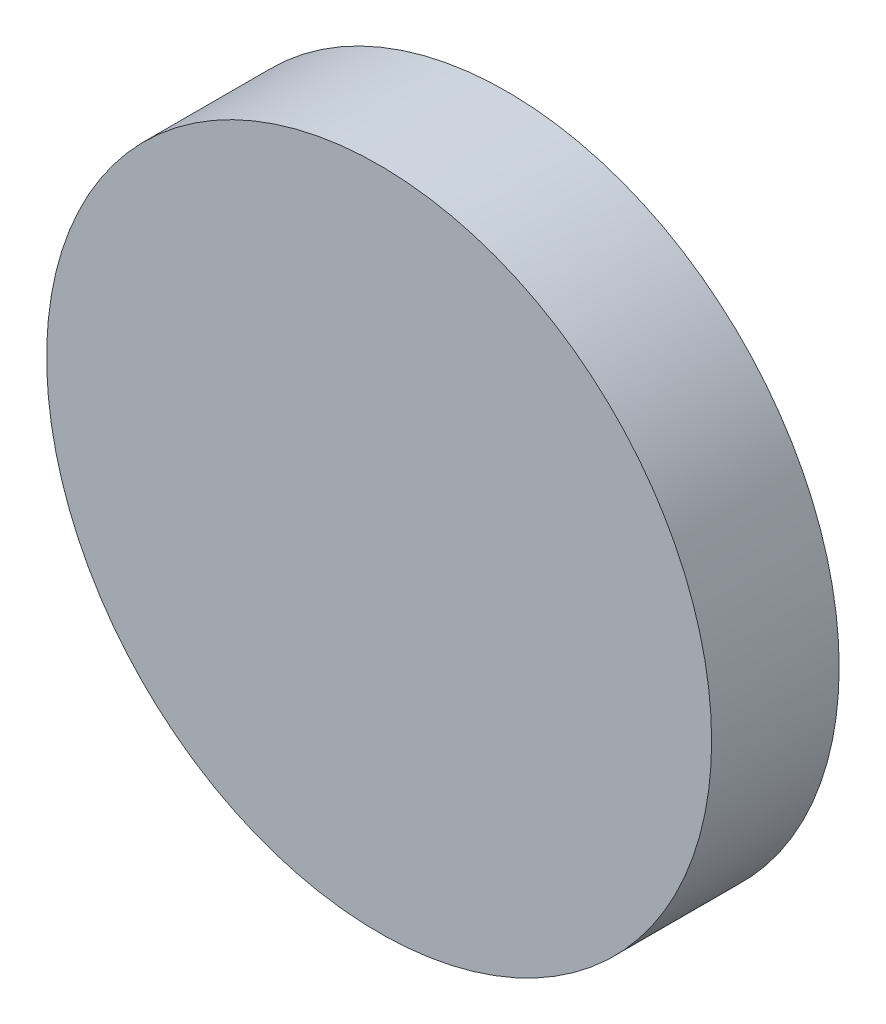
SolidWorks part; units mm, degrees
ref_plane "Front Plane" through (0, 0, 0) normal (0, 0, 1) x (1, 0, 0)
ref_plane "Top Plane" through (0, 0, 0) normal (0, 1, 0) x (1, 0, 0)
ref_plane "Right Plane" through (0, 0, 0) normal (1, 0, 0) x (0, 0, -1)
sketch "Sketch1" plane through (0, 0, 0) normal (1, 0, 0) x (0, 0, -1)
  line L0 (-53.8355, 0) -> (54.6766, 0) construction
  line L1 (-2.597, 0) -> (-2.597, 101)
  line L2 (-2.597, 101) -> (36.1452, 101)
  line L3 (36.1452, 101) -> (36.1452, 98)
  line L4 (36.1452, 98) -> (1.1452, 98)
  line L5 (1.1452, 98) -> (1.1452, 83)
  line L6 (1.1452, 83) -> (36.1452, 83)
  line L7 (36.1452, 83) -> (36.1452, 80)
  line L8 (36.1452, 80) -> (29.4831, 80)
  line L9 (0.403, 80) -> (0.403, 0)
  line L10 (0.403, 0) -> (-2.597, 0)
  line L11 (25.373, 80) -> (0.403, 80)
  line L13 (29.4831, 80) -> (29.4831, 81.2574)
  line L14 (29.4831, 81.2574) -> (25.373, 81.2574)
  line L15 (25.373, 80) -> (25.373, 81.2574)
  dimension "D1" = 101
  dimension "D2" = 3
  dimension "D3" = 3
  dimension "D4" = 80
  dimension "D5" = 3
  dimension "D6" = 35
  dimension "D7" = 35
revolve "Revolve1" add sketch "Sketch1" angle 360 about L0
